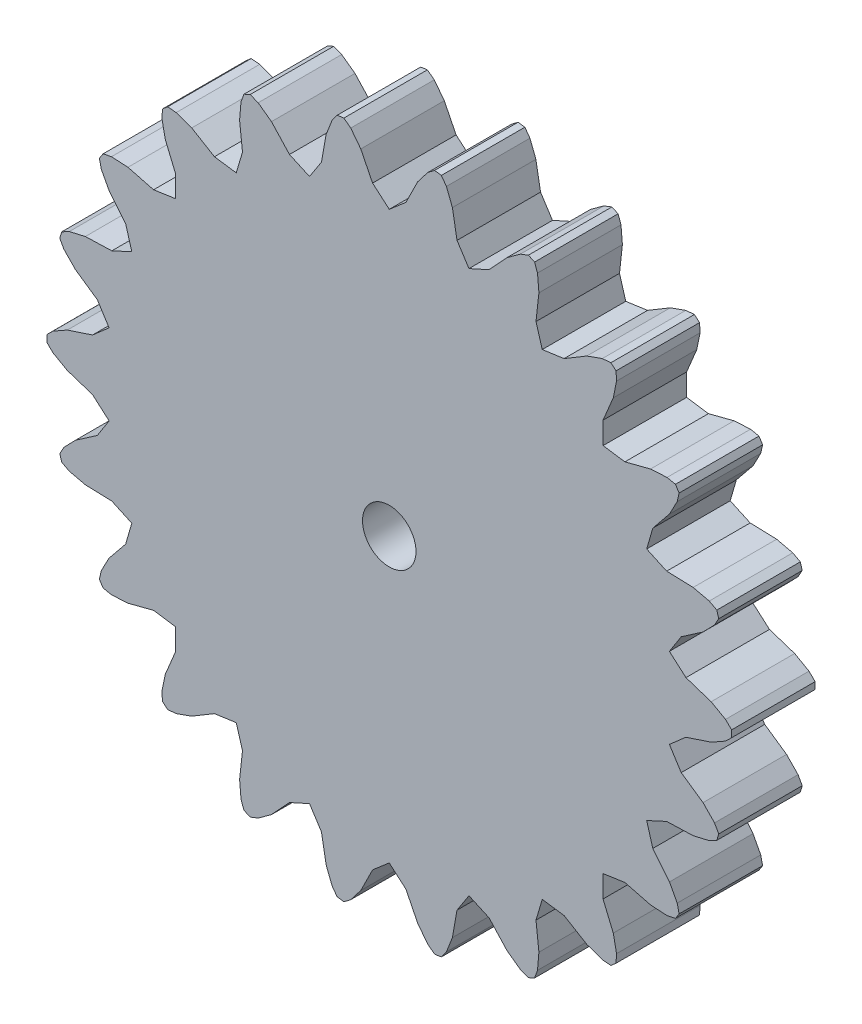
SolidWorks part; units mm, degrees
ref_plane "Front Plane" through (0, 0, 0) normal (0, 0, 1) x (1, 0, 0)
ref_plane "Top Plane" through (0, 0, 0) normal (0, 1, 0) x (1, 0, 0)
ref_plane "Right Plane" through (0, 0, 0) normal (1, 0, 0) x (0, 0, -1)
sketch "Sketch1" plane through (0, 0, 0) normal (0, 0, 1) x (1, 0, 0)
  line L1 (1.2374, -1.2374) -> (-1.2374, -1.2374) construction
  line L2 (1.2374, -1.2374) -> (1.2374, 1.2374) construction
  line L3 (1.2374, 1.2374) -> (-1.2374, 1.2374) construction
  line L4 (-1.2374, -1.2374) -> (-1.2374, 1.2374) construction
  line L5 (1.2374, -1.2374) -> (-1.2374, 1.2374) construction
  line L6 (1.2374, 1.2374) -> (-1.2374, -1.2374) construction
  circle A0 centre (0, 0) radius 20.5
  circle A1 centre (0, 0) radius 1.75 construction
  dimension "D1" = 41
  dimension "D2" = 3.5
extrude "Boss-Extrude1" add sketch "Sketch1" along normal blind 5
sketch "Sketch2" plane through (0, 0, 0) normal (0, 0, 1) x (1, 0, 0)
  line L0 (0, 0) -> (0, 10.088) construction
  line L1 (0, 16.9447) -> (-0.9985, 17.8041)
  line L8 (-2.7154, 20.3194) -> (0, 24.5037)
  line L11 (-0.9985, 17.8041) -> (-1.7043, 19.2252)
  line L12 (-1.7043, 19.2252) -> (-2.3066, 20.0063)
  line L13 (-2.3066, 20.0063) -> (-2.7154, 20.3194)
  line L14 (2.3066, 20.0063) -> (2.7154, 20.3194)
  line L15 (1.7043, 19.2252) -> (2.3066, 20.0063)
  line L16 (0.9985, 17.8041) -> (1.7043, 19.2252)
  line L17 (2.7154, 20.3194) -> (0, 24.5037)
  line L18 (0, 16.9447) -> (0.9985, 17.8041)
  circle A14 centre (0, 0) radius 20.5 construction
  point P16 (0, 20.5)
extrude "Cut-Extrude1" cut sketch "Sketch2" along normal through all
sketch "Sketch3" plane through (0, 0, 0) normal (0, 0, 1) x (1, 0, 0)
  circle A0 centre (0, 0) radius 7.5
  dimension "D1" = 15
sketch "Sketch4" plane through (0, 0, 5) normal (0, 0, 1) x (1, 0, 0)
  circle A0 centre (0, 0) radius 1.6
  dimension "D1" = 3.2
extrude "Cut-Extrude2" cut sketch "Sketch4" against normal through all both and the other way through all
pattern_circular "CirPattern1" count 22 over 360 about axis through (0, 0, 5) along (0, 0, -1) of "Cut-Extrude1" reverse direction yes
equation "\"circle\"=41"
equation "\"D1@Sketch1\"=\"circle\""
equation "\"separator_width\"=45"
equation "\"big-gear-thiccness\"=2"
equation "\"D1@Boss-Extrude1\"=10/2"
